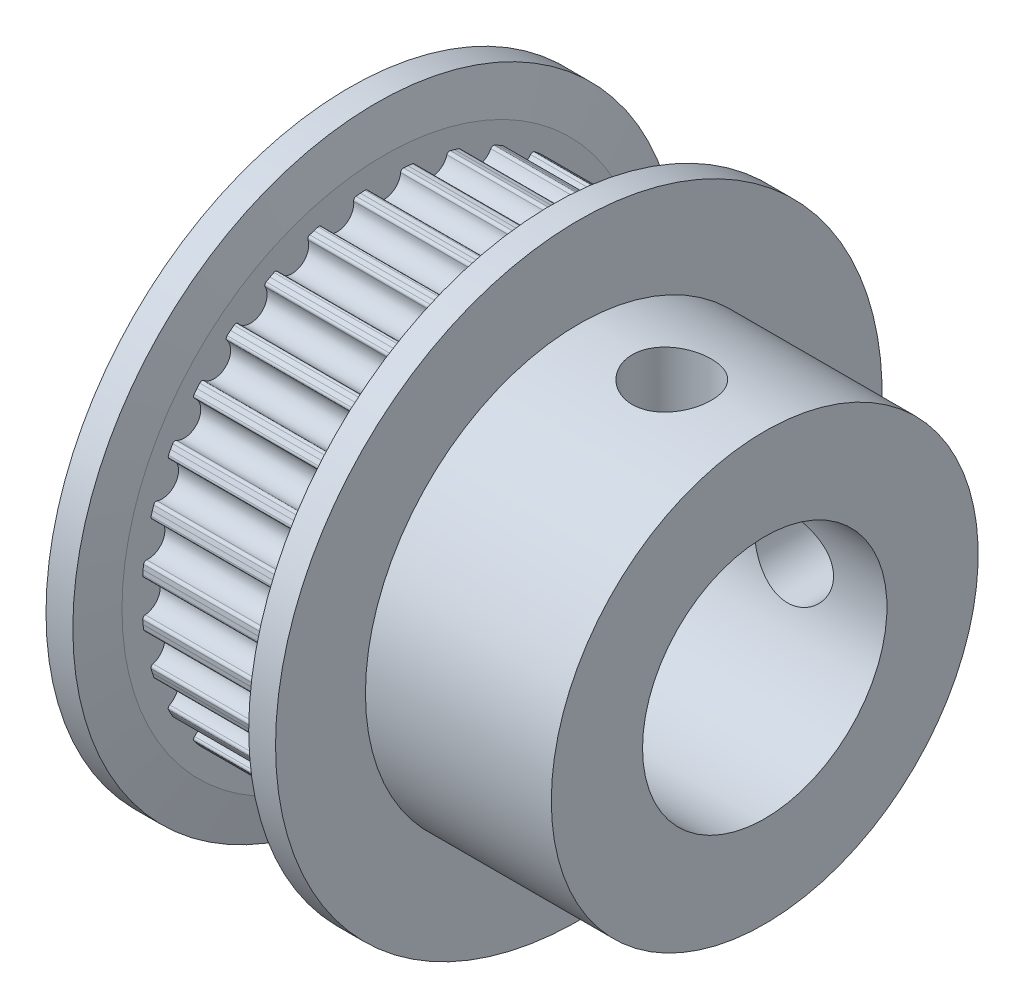
SolidWorks part; units mm, degrees
ref_plane "Front Plane" through (0, 0, 0) normal (0, 0, 1) x (1, 0, 0)
ref_plane "Top Plane" through (0, 0, 0) normal (0, 1, 0) x (1, 0, 0)
ref_plane "Right Plane" through (0, 0, 0) normal (1, 0, 0) x (0, 0, -1)
ref_plane "Plane1" through (0, 0, 0) normal (0, 0, 1) x (1, 0, 0)
sketch "Sketch1" plane through (0, 0, 0) normal (0, 0, 1) x (1, 0, 0)
  line L0 (0, 0) -> (0, 8.75)
  line L1 (0, 8.75) -> (1.43, 8.75)
  line L2 (1.43, 8.75) -> (1.43, 10.0881)
  line L3 (1.43, 10.0881) -> (7.98, 10.0881)
  line L4 (7.98, 10.0881) -> (7.98, 8.75)
  line L5 (7.98, 8.75) -> (17.03, 8.75)
  line L6 (17.03, 8.75) -> (17.03, 0)
  line L7 (17.03, 0) -> (0, 0)
  line L8 (17.03, 0) -> (0, 0) construction
  dimension "D1" = 6.55
  dimension "D2" = 8.75
  dimension "D3" = 1.43
  dimension "D4" = 9.05
  dimension "D5" = 10.0881
revolve "Revolve1" add sketch "Sketch1" angle 360 about L8 reverse direction yes
sketch "Sketch2" plane through (1.43, 0, 0) normal (1, 0, 0) x (0, 0, -1)
  line L0 (-1.0344, 9.88) -> (-1.0578, 10.1299)
  line L1 (-0.793, 9.8993) -> (-1.0344, 9.88)
  line L2 (0.793, 9.8993) -> (1.0344, 9.88)
  line L3 (1.0344, 9.88) -> (1.0578, 10.1299)
  line L4 (0, 10.185) -> (0, 0) construction
  arc A0 (-0.6724, 9.7974) -> (-0.793, 9.8993) centre (-0.784, 9.7876) ccw
  arc A1 (-0.6724, 9.7974) -> (0.6724, 9.7974) centre (0, 9.856) ccw
  arc A2 (0.6724, 9.7974) -> (0.793, 9.8993) centre (0.784, 9.7876) cw
  arc A3 (1.0578, 10.1299) -> (-1.0578, 10.1299) centre (0, 0) ccw
  dimension "D2" = 0.675
  dimension "D1" = 9.856
  dimension "D3" = 9.931
extrude "Cut-Extrude1" cut sketch "Sketch2" against normal up to surface (-6.55 mm away) up to face at (7.98, 0, 10.0881)
ref_axis "Axis1" through (17.03, 0, 0) along (-1, 0, 0)
pattern_circular "CirPattern1" count 32 over 360 about axis through (17.03, 0, 0) along (-1, 0, 0) of "Cut-Extrude1"
sketch "Sketch34" plane through (0, 0, 0) normal (0, 0, 1) x (1, 0, 0)
  line L0 (7.98, 8.75) -> (7.98, 10.75)
  line L1 (7.98, 10.75) -> (8.31, 12.435)
  line L2 (8.31, 12.435) -> (9.41, 12.435)
  line L3 (9.41, 12.435) -> (9.41, 8.75)
  line L4 (17.03, 8.75) -> (7.98, 8.75) construction
  line L5 (9.41, 8.75) -> (7.98, 8.75)
  line L6 (17.03, 0) -> (7.98, 0) construction
  line L7 (1.43, 8.75) -> (1.43, 10.75)
  line L8 (1.43, 10.75) -> (1.1, 12.435)
  line L9 (1.1, 12.435) -> (0, 12.435)
  line L10 (0, 12.435) -> (0, 8.76)
  line L11 (0.01, 8.75) -> (1.43, 8.75)
  line L12 (0, 8.76) -> (0.01, 8.75)
  point P16 (0, 8.75)
  dimension "D1" = 1.43
  dimension "D2" = 12.435
  dimension "D3" = 1.1
  dimension "D4" = 10.75
revolve "Revolve2" add sketch "Sketch34" angle 360 about L6 reverse direction yes
sketch "Sketch39" plane through (0, 0, 0) normal (-1, 0, 0) x (0, 0, 1)
  circle A0 centre (0, 0) radius 5.01
  dimension "D1" = 10.02
extrude "Cut-Extrude2" cut sketch "Sketch39" against normal up to surface (17.03 mm away) up to face at (17.03, 0, 8.75)
ref_plane "Plane39" through (13.22, 0, 0) normal (1, 0, 0) x (0, 0, -1)
sketch "Sketch37" plane through (13.22, 0, 0) normal (1, 0, 0) x (0, 0, -1)
  line L0 (0, 9.93) -> (1.621, 9.93)
  line L1 (1.621, 9.93) -> (1.621, 0)
  line L2 (1.621, 0) -> (0, 0)
  line L3 (0, 0) -> (0, 9.93)
  line L4 (0, 0) -> (0, 9.93) construction
revolve "Cut-Revolve2" cut sketch "Sketch37" angle 360 about L4 reverse direction yes
pattern_circular "CirPattern2" count 2 over 90 about axis through (17.03, 0, 0) along (-1, 0, 0) of "Cut-Revolve2"
